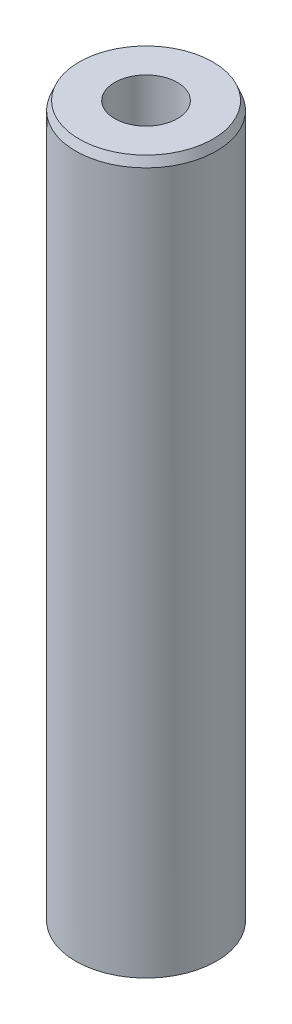
SolidWorks part; units mm, degrees
ref_plane "Front Plane" through (0, 0, 0) normal (0, 0, 1) x (1, 0, 0)
ref_plane "Top Plane" through (0, 0, 0) normal (0, 1, 0) x (1, 0, 0)
ref_plane "Right Plane" through (0, 0, 0) normal (1, 0, 0) x (0, 0, -1)
sketch "Sketch1" plane through (0, 0, 0) normal (0, 1, 0) x (1, 0, 0)
  circle A0 centre (0, 0) radius 37.5
  dimension "SHAFT_OD" = 75
extrude "Boss-Extrude1" add sketch "Sketch1" along normal blind 380.4406
sketch "Sketch2" plane through (0, 0, 0) normal (0, 1, 0) x (1, 0, 0)
  circle A0 centre (0, 0) radius 16.726
  dimension "BORE_D" = 33.452
extrude "Cut-Extrude1" cut sketch "Sketch2" along normal through all
chamfer "Chamfer1" distance 4.5923 angle 22.097 2 edges at (0, 380.4406, 37.5) (0, 0, 37.5) first distance on face at (0, 380.4406, 37.5) first distance on face at (0, 0, 16.726)
